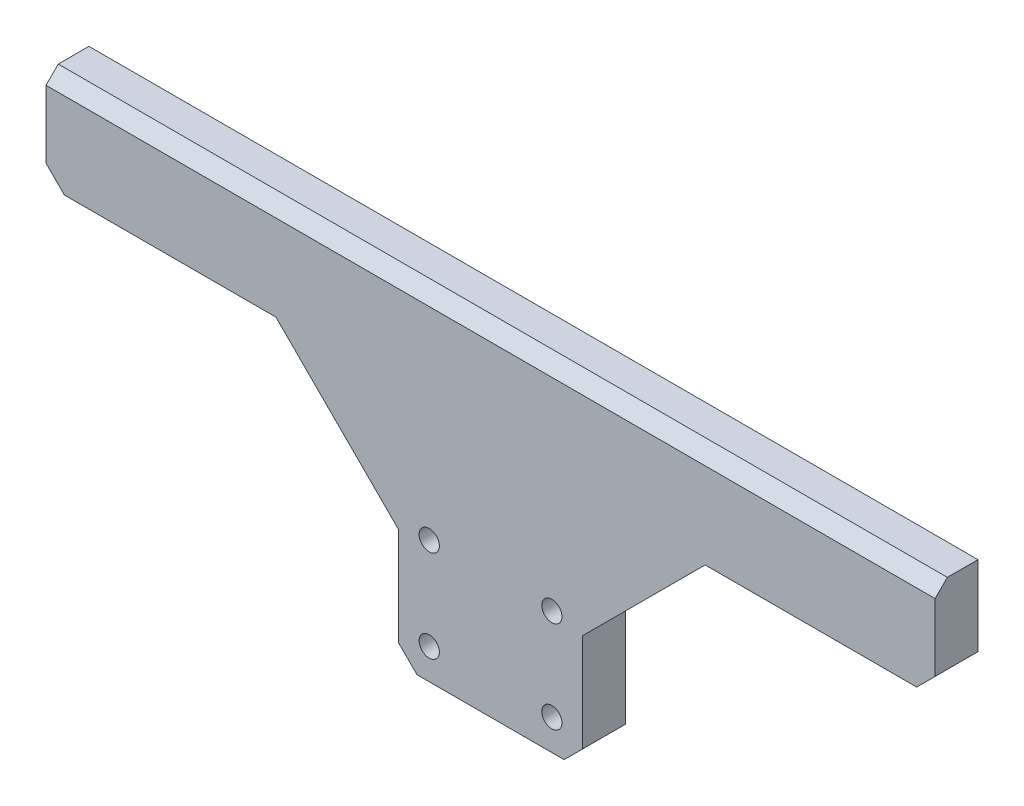
SolidWorks part; units mm, degrees
ref_plane "Front" through (0, 0, 0) normal (0, 0, 1) x (1, 0, 0)
ref_plane "Top" through (0, 0, 0) normal (0, 1, 0) x (1, 0, 0)
ref_plane "Right" through (0, 0, 0) normal (1, 0, 0) x (0, 0, -1)
sketch "Esquisse1" plane through (0, 0, 0) normal (0, 0, 1) x (1, 0, 0)
  line L1 (0, 0) -> (145, 0)
  line L2 (0, 0) -> (0, 25)
  line L3 (0, 25) -> (145, 25)
  line L4 (145, 0) -> (145, 25)
  dimension "D1" = 145
  dimension "D2" = 25
extrude "Boss.-Extru.1" add sketch "Esquisse1" along normal blind 7
sketch "Esquisse2" plane through (0, 0, 7) normal (0, 0, 1) x (1, 0, 0)
  line L0 (72.5, 0) -> (72.5, 25) construction
  line L1 (0, 0) -> (145, 0) construction
  line L2 (145, 25) -> (0, 25) construction
  line L3 (72.5, 12.5) -> (26.2893, 12.5) construction
  circle A0 centre (62.5, 20) radius 1.65
  circle A1 centre (62.5, 5) radius 1.65
  circle A2 centre (82.5, 5) radius 1.65
  circle A3 centre (82.5, 20) radius 1.65
  dimension "D1" = 20
  dimension "D2" = 15
  dimension "D3" = 3.3
extrude "Enlèv. mat.-Extru.1" cut sketch "Esquisse2" against normal through all both and the other way through all
sketch "Esquisse3" plane through (0, 0, 7) normal (0, 0, 1) x (1, 0, 0)
  line L0 (145, 0) -> (145, 25) construction
  line L1 (0, 25) -> (145, 25)
  line L2 (0, 25) -> (0, 55)
  line L3 (0, 55) -> (145, 55)
  line L4 (145, 25) -> (145, 55)
  dimension "D1" = 30
extrude "Boss.-Extru.2" add sketch "Esquisse3" against normal up to vertex (7 mm away) up to point (145, 25, 0)
chamfer "Chanfrein1" distance 2 angle 45 1 edges at (72.5, 55, 7)
sketch "Esquisse4" plane through (0, 0, 7) normal (0, 0, 1) x (1, 0, 0)
  line L0 (72.5, 0) -> (72.5, 55) construction
  line L1 (0, 0) -> (57.5, 0)
  line L2 (0, 0) -> (0, 39)
  line L3 (0, 39) -> (57.5, 39)
  line L4 (57.5, 0) -> (57.5, 39)
  line L5 (0, 0) -> (145, 0) construction
  line L6 (0, 55) -> (145, 55) construction
  line L7 (87.5, 0) -> (87.5, 39)
  line L8 (145, 39) -> (87.5, 39)
  line L9 (145, 0) -> (145, 39)
  line L10 (145, 0) -> (87.5, 0)
  dimension "D1" = 30
  dimension "D2" = 16
extrude "Enlèv. mat.-Extru.2" cut sketch "Esquisse4" against normal through all both and the other way through all
chamfer "Chanfrein2" distance 20 angle 45 2 edges at (87.5, 39, 3.5) (57.5, 39, 3.5)
chamfer "Chanfrein3" distance 3 angle 45 4 edges at (145, 39, 3.5) (87.5, 0, 3.5) (0, 39, 3.5) (57.5, 0, 3.5)
